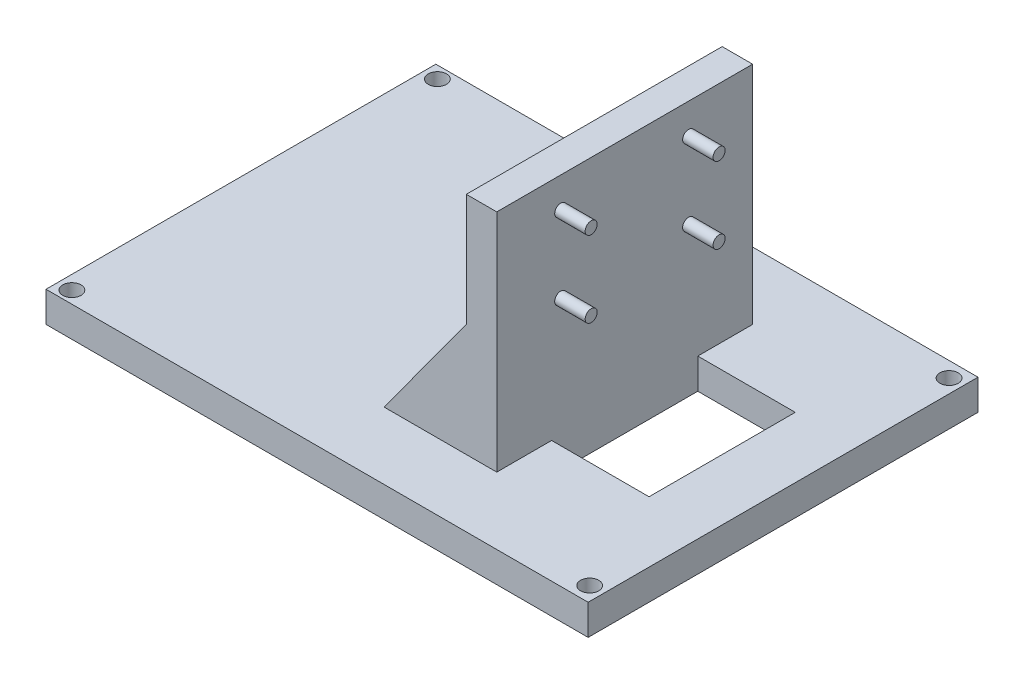
SolidWorks part; units mm, degrees
ref_plane "Front Plane" through (0, 0, 0) normal (0, 0, 1) x (1, 0, 0)
ref_plane "Top Plane" through (0, 0, 0) normal (0, 1, 0) x (1, 0, 0)
ref_plane "Right Plane" through (0, 0, 0) normal (1, 0, 0) x (0, 0, -1)
sketch "Sketch1" plane through (0, 0, 0) normal (0, 1, 0) x (1, 0, 0)
  line L0 (34.5, 12) -> (34.5, -12)
  line L1 (42.25, -29.5) -> (-42.25, -29.5) construction
  line L2 (42.25, -29.5) -> (42.25, 29.5) construction
  line L3 (42.25, 29.5) -> (-42.25, 29.5) construction
  line L4 (-42.25, -29.5) -> (-42.25, 29.5) construction
  line L5 (42.25, -29.5) -> (-42.25, 29.5) construction
  line L6 (42.25, 29.5) -> (-42.25, -29.5) construction
  line L7 (-42.25, -30) -> (42.25, -30) construction
  line L8 (-42.25, -30) -> (-42.25, 30) construction
  line L9 (-42.25, 30) -> (42.25, 30) construction
  line L10 (42.25, -30) -> (42.25, 30) construction
  line L11 (44.5, -32) -> (-44.5, -32)
  line L12 (44.5, -32) -> (44.5, 32)
  line L13 (44.5, 32) -> (-44.5, 32)
  line L14 (-44.5, -32) -> (-44.5, 32)
  line L15 (44.5, -32) -> (-44.5, 32) construction
  line L16 (44.5, 32) -> (-44.5, -32) construction
  line L17 (44.5, 12) -> (42.25, 12)
  line L18 (44.5, 12) -> (44.5, -12)
  line L19 (44.5, -12) -> (42.25, -12)
  line L20 (24.5, 12) -> (24.5, -12)
  line L21 (34.5, 12) -> (24.5, 12)
  line L22 (34.5, -12) -> (24.5, -12)
  line L24 (18.5, 21) -> (13.5, 21)
  line L25 (18.5, 21) -> (18.5, -21)
  line L26 (18.5, -21) -> (13.5, -21)
  line L27 (13.5, 21) -> (13.5, -21)
  circle A0 centre (42.25, -29.5) radius 1.5
  circle A1 centre (42.25, 29.5) radius 1.5
  circle A2 centre (-42.25, 30) radius 1.5
  circle A3 centre (-42.25, -30) radius 1.5
  point P0 (0, 0)
  point P14 (0, 0)
  dimension "D6" = 3
  dimension "D7" = 3
  dimension "D8" = 3
  dimension "D9" = 3
  dimension "D1" = 60
  dimension "D2" = 0.5
  dimension "D3" = 0.5
  dimension "D4" = 84.5
  dimension "D5" = 84.5
  dimension "D10" = 64
  dimension "D11" = 89
  dimension "D12" = 20
  dimension "D13" = 20
  dimension "D14" = 20
  dimension "D15" = 10
  dimension "D16" = 5
  dimension "D17" = 42
  dimension "D18" = 9
  dimension "D19" = 6
extrude "Boss-Extrude1" add sketch "Sketch1" along normal blind 5 contours L14 L11 L12 L13 A3 A2 A1 A0 L27 L24 L25 L26 L0 L22 L20 L21 | L24 L27 L26 L25 | L22 L0 L21 L20 region at (29.5, 0, 0) region at (-2.0009, 0, 0) region at (16, 0, 0)
extrude "Cut-Extrude1" cut sketch "Sketch1<3>" along normal through all contours L22 L20 L21 L0
sketch "Sketch1<3>" plane through (0, 0, 0) normal (0, 1, 0) x (1, 0, 0) same geometry as "Sketch1"
extrude "Boss-Extrude2" add sketch "Sketch1<4>" along normal blind 42 contours L25 L26 L27 L24
sketch "Sketch1<4>" plane through (0, 0, 0) normal (0, 1, 0) x (1, 0, 0) same geometry as "Sketch1"
sketch "Sketch3" plane through (0, 0, 0) normal (0, 0, 1) x (1, 0, 0)
  line L0 (13.5, 23.5) -> (0, 5)
  line L1 (13.5, 42) -> (13.5, 5) construction
  line L2 (44.5, 5) -> (-44.5, 5) construction
  line L3 (0, 5) -> (13.5, 5)
  line L4 (13.5, 5) -> (13.5, 23.5)
extrude "Boss-Extrude3" add sketch "Sketch3" along normal mid plane 42
sketch "Sketch4" plane through (24.5, 0, 0) normal (1, 0, 0) x (0, 0, -1)
  line L1 (-12, 5) -> (12, 5)
  line L2 (-12, 5) -> (-12, 0)
  line L3 (-12, 0) -> (12, 0)
  line L4 (12, 5) -> (12, 0)
extrude "Cut-Extrude2" cut sketch "Sketch4" against normal blind 6
sketch "Sketch5" plane through (18.5, 0, 0) normal (1, 0, 0) x (0, 0, -1)
  line L0 (21, 42) -> (21, 5) construction
  line L1 (-10.5, 37) -> (10.5, 37) construction
  line L2 (-10.5, 37) -> (-10.5, 24.5) construction
  line L3 (-10.5, 24.5) -> (10.5, 24.5) construction
  line L4 (10.5, 37) -> (10.5, 24.5) construction
  line L5 (21, 42) -> (-21, 42) construction
  circle A0 centre (-10.5, 37) radius 0.99
  circle A1 centre (10.5, 37) radius 0.99
  circle A2 centre (10.5, 24.5) radius 0.99
  circle A3 centre (-10.5, 24.5) radius 0.99
  dimension "D5" = 1.98
  dimension "D1" = 12.5
  dimension "D2" = 21
  dimension "D3" = 10.5
  dimension "D4" = 5
  dimension "D6" = 2
  dimension "D7" = 2
  dimension "D8" = 2
extrude "Boss-Extrude4" add sketch "Sketch5" along normal blind 5
